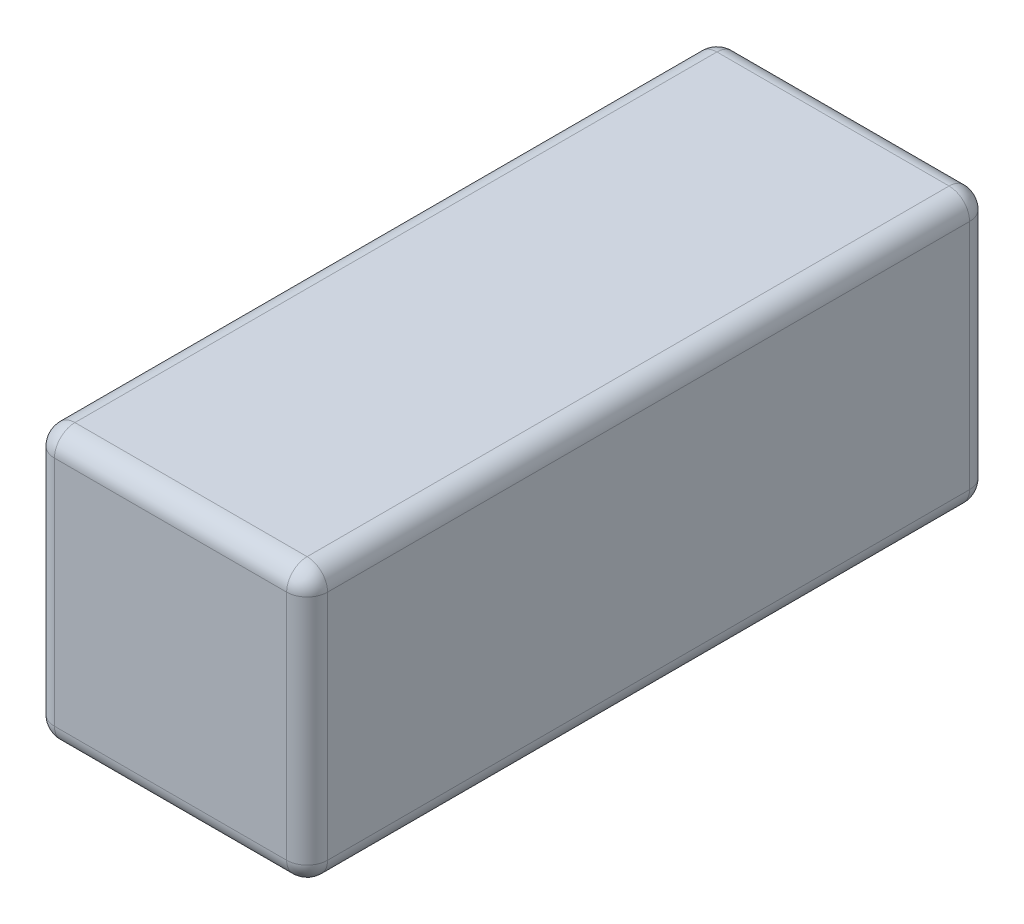
SolidWorks part; units mm, degrees
ref_plane "Front Plane" through (0, 0, 0) normal (0, 0, 1) x (1, 0, 0)
ref_plane "Top Plane" through (0, 0, 0) normal (0, 1, 0) x (1, 0, 0)
ref_plane "Right Plane" through (0, 0, 0) normal (1, 0, 0) x (0, 0, -1)
sketch "Sketch1" plane through (0, 0, 0) normal (0, 0, 1) x (1, 0, 0)
  line L3 (1, -1) -> (-1, -1)
  line L4 (1, -1) -> (1, 1)
  line L5 (1, 1) -> (-1, 1)
  line L6 (-1, -1) -> (-1, 1)
  line L7 (1, -1) -> (-1, 1) construction
  line L8 (1, 1) -> (-1, -1) construction
  point P0 (0, 0)
  dimension "Width" = 2
  dimension "Height" = 2
sketch "Sketch2" plane through (0, 0, 0) normal (1, 0, 0) x (0, 0, -1)
  line L2 (5, -1) -> (-5, -1)
  line L3 (5, -1) -> (5, 1)
  line L4 (5, 1) -> (-5, 1)
  line L5 (-5, -1) -> (-5, 1)
  line L6 (5, -1) -> (-5, 1) construction
  line L7 (5, 1) -> (-5, -1) construction
  point P0 (0, 0)
  point P4 (0, 0)
  point P15 (-2.8, 1)
  point P17 (2.8, 1)
  dimension "Length" = 10
  dimension "D1" = 2.2
  dimension "D2" = 2.2
sketch "Sketch3" plane through (0, 0, 0) normal (0, 0, 1) x (1, 0, 0)
  line L0 (1, -1) -> (1, 1) construction
  line L5 (1, -1) -> (-1, -1) construction
  line L6 (-1, -1) -> (-1, 1) construction
  line L7 (1, 1) -> (-1, 1) construction
  line L8 (1, -1) -> (1, 1)
  line L9 (1, -1) -> (-1, -1)
  line L10 (-1, -1) -> (-1, 1)
  line L11 (1, 1) -> (-1, 1)
extrude "Boss-Extrude1" add sketch "Sketch3" along normal up to vertex (5 mm away) and the other way up to vertex (5 mm away) up to point (0, 1, 5) other way up to point (0, 1, -5)
fillet "Fillet2" radius 0.15 12 edges at (-1, 0, -5) (0, -1, -5) (-1, 1, 0) (0, 1, -5) (1, 1, 0) (1, 0, -5) (1, -1, 0) (-1, 0, 5) (0, 1, 5) (1, 0, 5) (0, -1, 5) (-1, -1, 0)
ref_plane "Contact Plane 1" through (0, 0, 5) normal (0, 0, 1) x (1, 0, 0)
ref_plane "Contact Plane 2" through (0, 0, -5) normal (0, 0, 1) x (1, 0, 0)
ref_axis "Center Axis 1" through (0, 0, -27.5) along (0, 0, 1)
sketch "Sketch4" plane through (0, 0, -5) normal (0, 0, -1) x (-1, 0, 0)
  line L0 (1, 0.85) -> (1, -0.85) construction
  line L1 (-1, -1) -> (1, -1)
  line L2 (-1, -1) -> (-1, 1)
  line L3 (-1, 1) -> (1, 1)
  line L4 (1, -1) -> (1, 1)
  line L5 (-1, -1) -> (1, 1) construction
  line L6 (-1, 1) -> (1, -1) construction
  line L7 (-0.85, 1) -> (0.85, 1) construction
  point P0 (0, 0)
extrude "Cut-Extrude1" cut sketch "Sketch4" against normal blind 5
fillet "Fillet3" radius 0.15 8 edges at (-0.9561, 0.9561, 0) (-1, 0, 0) (-0.9561, -0.9561, 0) (0, -1, 0) (0.9561, -0.9561, 0) (1, 0, 0) (0.9561, 0.9561, 0) (0, 1, 0)
equation "\"D1@Sketch2\"=\"Width@Sketch1\"*1.1"
equation "\"D2@Sketch2\"=\"D1@Sketch2\""
